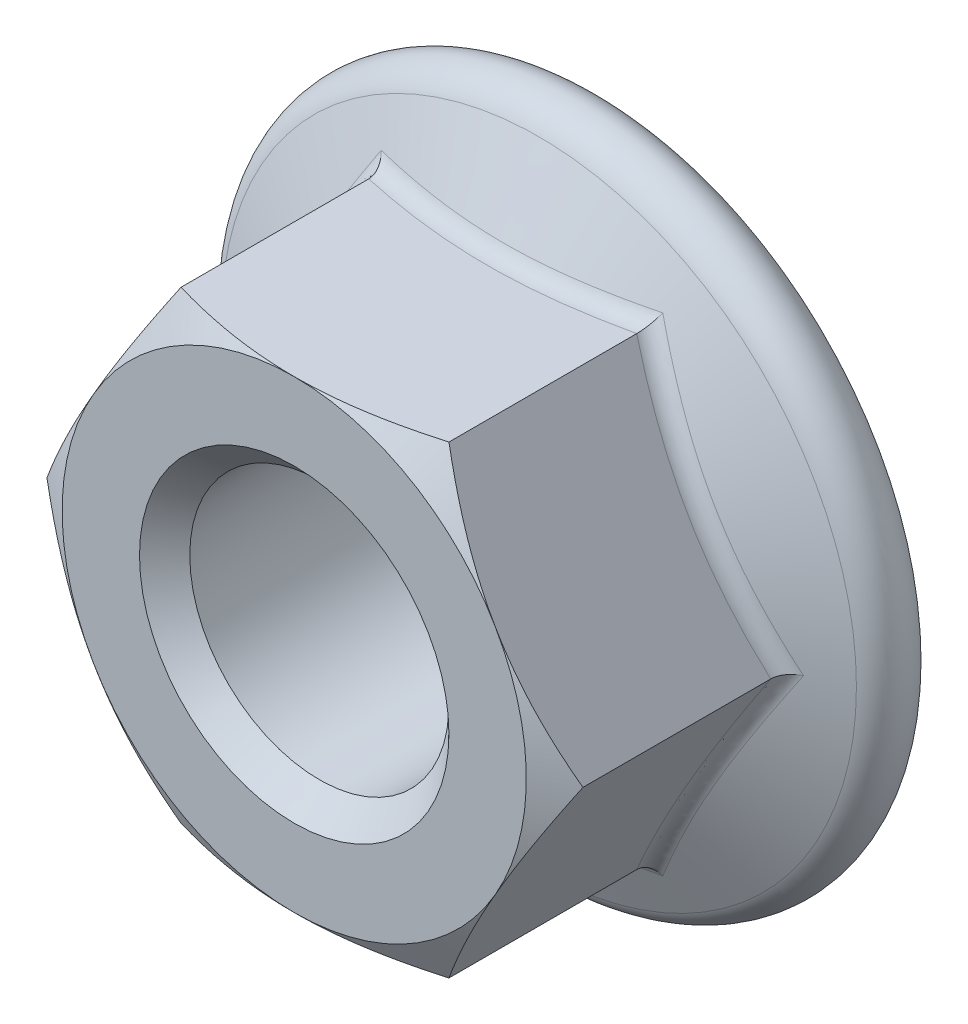
SolidWorks part; units mm, degrees
ref_plane "Front" through (0, 0, 0) normal (0, 0, 1) x (1, 0, 0)
ref_plane "Top" through (0, 0, 0) normal (0, 1, 0) x (1, 0, 0)
ref_plane "Right" through (0, 0, 0) normal (1, 0, 0) x (0, 0, -1)
sketch "Sketch1" plane through (0, 0, 0) normal (0, 0, 1) x (1, 0, 0)
  line L1 (4.3301, -7.5) -> (8.6603, 0)
  line L2 (8.6603, 0) -> (4.3301, 7.5)
  line L3 (4.3301, 7.5) -> (-4.3301, 7.5)
  line L4 (-4.3301, 7.5) -> (-8.6603, 0)
  line L5 (-8.6603, 0) -> (-4.3301, -7.5)
  line L6 (-4.3301, -7.5) -> (4.3301, -7.5)
  circle A0 centre (0, 0) radius 7.5 construction
  circle A1 centre (0, 0) radius 4.188
  dimension "D1" = 8.376
  dimension "s" = 15
extrude "BaseNut" add sketch "Sketch1" against normal blind 10
cosmetic thread "ThreadCosmetic1" [suppressed] parameters "D2"=10
sketch "Sketch3" plane through (0.6779, 0, -16.6426) normal (0, 1, 0) x (0, 0, -1)
  line L0 (4.0352, 0.6779) -> (-19.0613, 0.6779) construction
  line L2 (-16.6426, 8.1779) -> (-15.9728, 9.3381)
  line L4 (-15.9728, 9.3381) -> (-16.6426, 9.3381)
  line L5 (-16.6426, 9.3381) -> (-16.6426, 8.1779)
  line L6 (-11.6426, 9.3381) -> (-11.6426, 14.238) construction
  line L8 (-6.6426, 9.3381) -> (-6.6426, 8.1779)
  line L9 (-7.3125, 9.3381) -> (-6.6426, 9.3381)
  line L10 (-6.6426, 8.1779) -> (-7.3125, 9.3381)
  line L11 (-6.6426, 9.3381) -> (-16.6426, 9.3381) construction
  dimension "D1" = 30
  dimension "sq" = 15
revolve "Double-Chamfer" cut sketch "Sketch3" angle 360 about L0
sketch "Sketch4" plane through (4.6827, 0, -16.7173) normal (0, 1, 0) x (0, 0, -1)
  line L0 (-21.7744, 4.6827) -> (9.7398, 4.6827) construction
  line L2 (-11.6479, 30.5008) -> (-11.6479, 8.9315) construction
  line L3 (-8.8143, 14.9476) -> (-11.6479, 8.8707)
  line L4 (-6.7173, 8.8707) -> (-16.7173, 8.8707) construction
  line L5 (-6.7173, 8.8707) -> (-6.7173, 14.4827)
  line L11 (-11.6479, 8.8707) -> (-6.7173, 8.8707)
  arc A0 (-6.7173, 14.4827) -> (-8.8143, 14.9476) centre (-7.8173, 14.4827) ccw
  dimension "m1" = 10
  dimension "dc" = 21.8
  dimension "dw" = 19.6
  dimension "&" = 25
revolve "Flange" add sketch "Sketch4" angle 360 about L0
fillet "FlangeFillet" radius 0.6 6 edges at (-5.4879, -5.4947, -6.7378) (-7.5025, 2.0053, -6.7378) (5.4879, 5.4947, -6.7378) (7.5025, -2.0053, -6.7378)
sketch "Sketch5" plane through (-5.1971, 0, -15.1971) normal (0, 1, 0) x (0, 0, -1)
  line L0 (3.5984, -5.1971) -> (-23.9926, -5.1971) construction
  line L1 (-5.1971, -1.0091) -> (-15.1971, -1.0091) construction
  line L2 (-15.1971, -0.1971) -> (-15.1971, -1.0091)
  line L4 (-15.1971, -1.0091) -> (-14.3851, -1.0091)
  line L6 (-14.3851, -1.0091) -> (-15.1971, -0.1971)
  line L7 (-10.1971, -1.0091) -> (-10.1971, 0.9419) construction
  line L8 (-6.0091, -1.0091) -> (-5.1971, -0.1971)
  line L9 (-5.1971, -1.0091) -> (-6.0091, -1.0091)
  line L10 (-5.1971, -0.1971) -> (-5.1971, -1.0091)
  dimension "da" = 10
  dimension "D2" = 45
revolve "Hole" cut sketch "Sketch5" angle 360 about L0
sketch "Sketch6" plane through (0, 0, 0) normal (0, 1, 0) x (1, 0, 0)
  line L0 (-4.8912, 0.812) -> (-4.188, 0.406)
  line L1 (-4.188, 0.406) -> (-3.376, 0.406)
  line L2 (-3.376, 0.406) -> (-3.376, 1.218)
  line L3 (-3.376, 1.218) -> (-4.188, 1.218)
  line L4 (-4.188, 1.218) -> (-4.8912, 0.812)
  line L5 (0, 7.348) -> (0, 34.1252) construction
  dimension "D1" = 0.812
  dimension "D2" = 8.376
revolve "Cut-Revolve10" [suppressed] cut sketch "Sketch6" angle 360 about L5
pattern_linear "LPattern10" [suppressed] count 10 spacing 0.9744 along (0, 0, -1) of bodies 105
equation "\"m1@Sketch4\" = \"m@BaseNut\""
equation "\"sq@Sketch3\" = \"s@Sketch1\""
equation "\"D2@Sketch6\"=\"D1@Sketch1\""
equation "\"D1@Sketch6\"= (\"D2@ThreadCosmetic1\"  - \"D2@Sketch6\" )  / 2"
equation "\"D3@LPattern10\"=\"D1@Sketch6\" * 1.2 "
equation "\"D1@LPattern10\"=\"m@BaseNut\"  / \"D3@LPattern10\""
